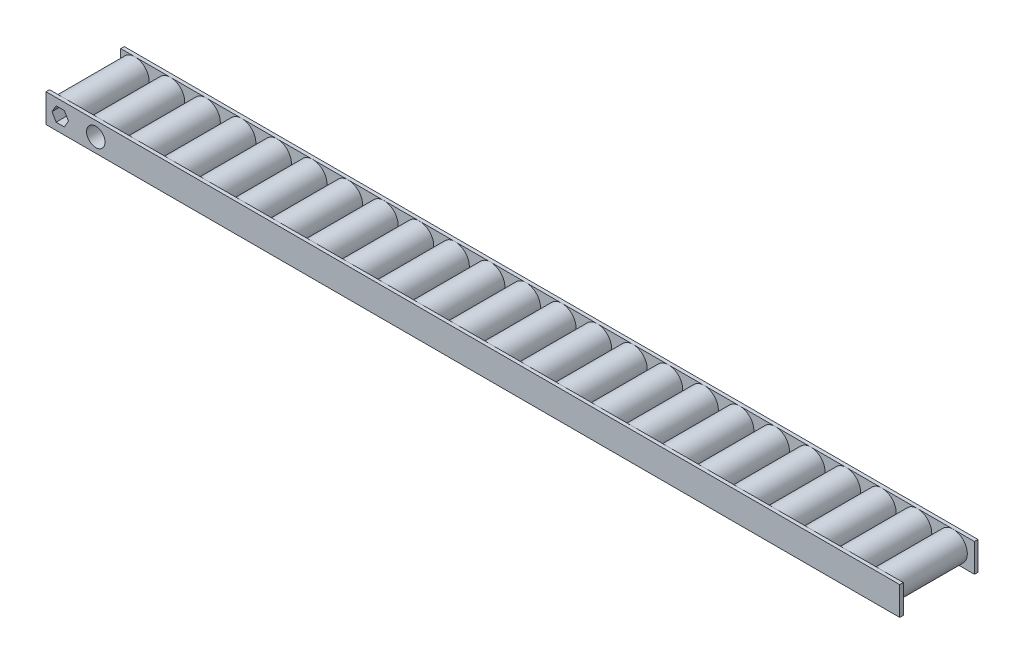
SolidWorks part; units mm, degrees
note: '?' marks a value the reader was unsure of.
material "6061 Alloy"
ref_plane "Front Plane" through (0, 0, 0) normal (0, 0, 1) x (1, 0, 0)
ref_plane "Top Plane" through (0, 0, 0) normal (0, 1, 0) x (1, 0, 0)
ref_plane "Right Plane" through (0, 0, 0) normal (1, 0, 0) x (0, 0, -1)
sketch "Sketch1" plane through (0, 0, 0) normal (0, 0, 1) x (1, 0, 0)
  circle A0 centre (0, 0) radius 12.7
  dimension "D1" = 25.4
extrude "Boss-Extrude1" add sketch "Sketch1" along normal blind 63.5 contours A0
pattern_linear "LPattern1" count 24 spacing 31.75 along (1, 0, 0) of "Boss-Extrude1"
sketch "Sketch2" plane through (0, 0, 63.5) normal (0, 0, 1) x (1, 0, 0)
  line L0 (-12.7, 12.7) -> (-12.7, -12.7)
  line L1 (-12.7, -12.7) -> (749.3, -12.7)
  line L2 (749.3, -12.7) -> (749.3, 12.7)
  line L3 (749.3, 12.7) -> (-12.7, 12.7)
  dimension "D1" = 762
  dimension "D2" = 25.4
extrude "Boss-Extrude2" add sketch "Sketch2" along normal blind 3.175
ref_plane "Plane1" through (0, 0, 31.75) normal (0, 0, 1) x (1, 0, 0)
mirror "Mirror1" about plane through (0, 0, 31.75) normal (0, 0, 1) of "Boss-Extrude2"
sketch "Sketch3" plane through (0, 0, 66.675) normal (0, 0, 1) x (1, 0, 0)
  line L1 (7.3323, 0) -> (3.6662, 6.35)
  line L2 (31.75, -12.7) -> (63.5, -12.7)
  line L3 (63.5, 12.7) -> (31.75, 12.7)
  line L6 (3.6662, 6.35) -> (-3.6662, 6.35)
  line L7 (-3.6662, 6.35) -> (-7.3323, 0)
  line L8 (-7.3323, 0) -> (-3.6662, -6.35)
  line L9 (-3.6662, -6.35) -> (3.6662, -6.35)
  line L10 (3.6662, -6.35) -> (7.3323, 0)
  arc A0 (0, 12.7) -> (-12.7, 0) centre (0, 0) ccw construction
  arc A1 (0, -12.7) -> (0, 12.7) centre (0, 0) ccw construction
  arc A2 (31.75, -12.7) -> (31.75, 12.7) centre (31.75, 0) ccw
  arc A3 (63.5, 12.7) -> (63.5, -12.7) centre (63.5, 0) ccw
  arc A4 (31.75, -12.7) -> (31.75, 12.7) centre (31.75, 0) ccw construction
  arc A6 (31.75, 12.7) -> (31.75, -12.7) centre (31.75, 0) ccw construction
  arc A7 (0, 12.7) -> (-12.7, 0) centre (0, 0) ccw construction
  arc A8 (0, -12.7) -> (0, 12.7) centre (0, 0) ccw construction
  arc A9 (31.75, 12.7) -> (31.75, -12.7) centre (31.75, 0) ccw construction
  circle A10 centre (31.75, 0) radius 8.255
  circle A11 centre (0, 0) radius 6.35 construction
  dimension "D2" = 16.51
  dimension "D3" = 12.7
  dimension "D1" = 0
extrude "Cut-Extrude1" cut sketch "Sketch3" against normal through all
ref_axis "Axis1" through (539.75, 0, 63.5) along (0, 0, -1)?
ref_axis "Axis2" through (571.5, 0, 63.5) along (0, 0, -1)?
ref_axis "Axis3" through (603.25, 0, 63.5) along (0, 0, -1)?
sketch "Sketch4" plane through (0, 0, 66.675) normal (0, 0, 1) x (1, 0, 0)
  circle A0 centre (730.25, 0) radius 9.525
  circle A1 centre (730.25, 0) radius 12.7
  circle A2 centre (730.25, 0) radius 12.7 construction
  dimension "D1" = 0
